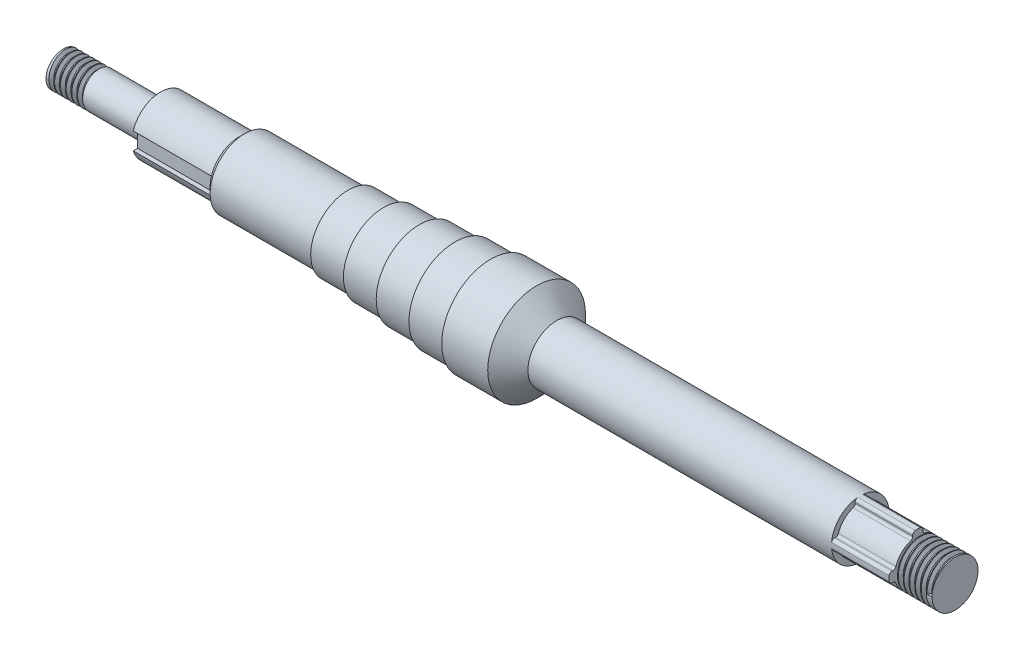
SolidWorks part; units mm, degrees
ref_plane "Front Plane" through (0, 0, 0) normal (0, 0, 1) x (1, 0, 0)
ref_plane "Top Plane" through (0, 0, 0) normal (0, 1, 0) x (1, 0, 0)
ref_plane "Right Plane" through (0, 0, 0) normal (1, 0, 0) x (0, 0, -1)
sketch "Sketch1" plane through (0, 0, 0) normal (0, 0, 1) x (1, 0, 0)
  line L0 (0, 0) -> (155.16, 0) construction
  line L4 (0, 0) -> (0, 3)
  line L5 (0, 3) -> (6.5, 3)
  line L11 (31.55, 6) -> (49.55, 6)
  line L12 (49.55, 6) -> (49.55, 6.5)
  line L13 (49.55, 6.5) -> (55.75, 6.5)
  line L17 (61.95, 7.5) -> (68.15, 7.5)
  line L18 (68.15, 7.5) -> (68.15, 8)
  line L31 (31.55, 6) -> (49.55, 6)
  line L36 (0, 0) -> (155.16, 0)
  line L38 (20.87, 5) -> (30.55, 5)
  line L40 (30.55, 5) -> (31.55, 6)
  line L41 (68.15, 8) -> (74.35, 8)
  line L42 (74.35, 8.5) -> (74.35, 8)
  line L43 (74.35, 8.5) -> (82.35, 8.5)
  line L44 (55.75, 6.5) -> (55.75, 7)
  line L45 (55.75, 7) -> (61.95, 7)
  line L46 (111.66, 5) -> (148.66, 5)
  line L47 (61.95, 7) -> (61.95, 7.5)
  line L48 (82.35, 8.5) -> (85.85, 5)
  line L49 (85.85, 5) -> (111.66, 5)
  line L50 (148.66, 5) -> (148.66, 4)
  line L51 (148.66, 4) -> (155.16, 4)
  line L52 (155.16, 4) -> (155.16, 0)
  line L54 (6.5, 3) -> (16.94, 3)
  line L55 (16.94, 3) -> (16.94, 5)
  line L56 (16.94, 5) -> (20.87, 5)
  dimension "D13" = 3
  dimension "D12" = 6.5
  dimension "D5" = 9.68
  dimension "D6" = 5
  dimension "D7" = 6
  dimension "D8" = 45
  dimension "D9" = 18
  dimension "D10" = 6.2
  dimension "D3" = 6.2
  dimension "D4" = 6.2
  dimension "D15" = 8
  dimension "D18" = 8.5
  dimension "D11" = 25.81
  dimension "D19" = 5
  dimension "D20" = 45
  dimension "D21" = 6.2
  dimension "D16" = 37
  dimension "D17" = 4
  dimension "D22" = 6.5
  dimension "D14" = 10.44
  dimension "D23" = 3.93
revolve "Revolve1" add sketch "Sketch1" angle 360 about L0
sketch3d "3DSketch1" plane through (0, 0, 0) normal (0, 0, 1) x (1, 0, 0)
thread "Thread1" pitch 1 method cut trim with end face yes profile "Thread Profile1" start angle 0, offset 0, length 0, pitch 1, diameter 8
ref_plane "Plane1" through (155.16, 0, 4) normal (0, -1, 0) x (0, 0, 1)
sketch "Thread Profile1" plane through (155.16, 0, 4) normal (0, -1, 0) x (0, 0, 1)
  line L0 (0, 0) -> (0, 1) construction
  line L11 (0, 0) -> (0, 0.875)
  line L12 (0, 0.875) -> (-0.5413, 0.5625)
  line L13 (-0.5413, 0.5625) -> (-0.5413, 0.3125)
  line L15 (-0.5413, 0.3125) -> (0, 0)
  line L17 (-0.5413, 0.4375) -> (0, 0.4375) construction
  point P2 (0, 0)
  dimension "Pitch" = 1
  dimension "Profile_Angle" = 60
  dimension "Profile_Land" = 0.25
  dimension "Profile_Height" = 0.5413
thread "Thread2" pitch 1 method cut profile "Thread Profile2" start angle 0, offset 0, length 0, pitch 1, diameter 6
ref_plane "Plane2" through (0, 0, -3) normal (0, -1, 0) x (0, 0, -1)
sketch "Thread Profile2" plane through (0, 0, -3) normal (0, -1, 0) x (0, 0, -1)
  line L0 (0, 0) -> (0, 1) construction
  line L11 (0, 0) -> (0, 0.875)
  line L12 (0, 0.875) -> (-0.5413, 0.5625)
  line L13 (-0.5413, 0.5625) -> (-0.5413, 0.3125)
  line L15 (-0.5413, 0.3125) -> (0, 0)
  line L17 (-0.5413, 0.4375) -> (0, 0.4375) construction
  point P2 (0, 0)
  dimension "Pitch" = 1
  dimension "Profile_Angle" = 60
  dimension "Profile_Land" = 0.25
  dimension "Profile_Height" = 0.5413
sketch "Sketch7" plane through (148.66, 0, 0) normal (1, 0, 0) x (0, 0, -1)
  line L0 (-0.881, 3.9018) -> (-0.881, 4.9218)
  line L1 (0.881, 3.9018) -> (0.881, 4.9218)
  line L2 (3.9018, 0.881) -> (4.9218, 0.881)
  line L3 (3.9018, -0.881) -> (4.9218, -0.881)
  line L4 (0.881, -3.9018) -> (0.881, -4.9218)
  line L5 (-0.881, -3.9018) -> (-0.881, -4.9218)
  line L6 (-3.9018, -0.881) -> (-4.9218, -0.881)
  line L7 (-3.9018, 0.881) -> (-4.9218, 0.881)
  circle A0 centre (0, 0) radius 4
  circle A1 centre (0, 0) radius 5 construction
  point P24 (0, 0)
  arc M3 (4, 0) -> (2.8284, -2.8284) centre (0, 0) cw
  circle M7 centre (0, 0) radius 5
  dimension "D1" = 8
  dimension "D2" = 1.02
  dimension "D3" = 4
extrude "Cut-Extrude2" cut sketch "Sketch7" against normal blind 10 contours A0 L2 L1 M7 | L4 L3 M7 M3 | A0 L6 L5 M7 | A0 L0 L7 M7 region at (148.66, 3.0174, 3.0174) region at (148.66, 3.0174, -3.0174) region at (148.66, -3.0174, 3.0174) region at (148.66, -3.0174, -3.0174)
fillet "Fillet1" radius 0.5 16 edges at (143.66, 0.881, -4.9218) (143.66, -0.881, 3.9018) (143.66, 3.9018, 0.881) (143.66, 0.881, 3.9018) (143.66, 0.881, 4.9218) (143.66, -0.881, 4.9218) (143.66, -3.9018, 0.881) (143.66, -4.9218, 0.881) (143.66, -3.9018, -0.881) (143.66, -4.9218, -0.881) (143.66, -0.881, -3.9018) (143.66, 0.881, -3.9018) (143.66, 3.9018, -0.881) (143.66, 4.9218, 0.881) (143.66, 4.9218, -0.881) (143.66, -0.881, -4.9218)
sketch "Sketch8" plane through (16.94, 0, 0) normal (-1, 0, 0) x (0, 0, 1)
  line L0 (-4.7697, 1.5) -> (-4, 1.5)
  line L1 (-4, 1.5) -> (-4, -1.5)
  line L2 (-4, -1.5) -> (-4.7697, -1.5)
  circle A0 centre (0, 0) radius 5 construction
  circle A1 centre (0, 0) radius 5 construction
  circle A4 centre (0, 0) radius 5
  point P14 (0, 0)
  point P15 (0, 0)
  dimension "D1" = 4
  dimension "D2" = 3
extrude "Cut-Extrude6" cut sketch "Sketch8" against normal blind 13.61 and the other way through all flip side to cut contours L0 L1 L2
pattern_circular "CirPattern1" count 2 over 360 about axis through (0, 0, 0) along (-1, 0, 0) of "Cut-Extrude6"
equation "\"Lab_Seal_Height\"= 0.089mm"
equation "\"Lab_Seal_Width\"= 12.7mm"
equation "\"LOx_Nut_Rad\"= 3mm"
equation "\"LOx_Nut_Len\"= 6.5mm"
equation "\"LOx_Taper_Len\"= 15.24mm"
equation "\"D13@Sketch1\"=\"LOx_Nut_Rad\""
equation "\"D12@Sketch1\"=\"LOx_Nut_Len\""
equation "\"LOx_Section_2\"= 9.68"
equation "\"LOx_End_Taper_Ang\"= 45deg"
equation "\"LOx_End_Rad\"= 5mm"
equation "\"D6@Sketch1\"=\"LOx_End_Rad\""
equation "\"D5@Sketch1\"=\"LOx_Section_2\""
equation "\"LOx_Bearing_Rad\"= 6mm"
equation "\"LOx_Bearing_Section_Width\"= 18mm"
equation "\"Lab_Seal_Len\"= 6.2mm"
equation "\"Lab_Seal_Stepup\"= .5"
equation "\"D7@Sketch1\"=\"LOx_Bearing_Rad\""
equation "\"D8@Sketch1\"=\"LOx_End_Taper_Ang\""
equation "\"D9@Sketch1\"=\"LOx_Bearing_Section_Width\""
equation "\"D10@Sketch1\"=\"Lab_Seal_Len\""
equation "\"D3@Sketch1\"=\"Lab_Seal_Len\""
equation "\"D4@Sketch1\"=\"Lab_Seal_Len\""
equation "\"Center_Section_Len\"= 8mm"
equation "\"Center_Section_Rad\"= 8.5mm"
equation "\"D15@Sketch1\"=\"Center_Section_Len\""
equation "\"D18@Sketch1\"=\"Center_Section_Rad\""
equation "\"Kero_Len\"= 25.81"
equation "\"Kero_Rad\"= 5mm"
equation "\"D11@Sketch1\"=\"Kero_Len\""
equation "\"D19@Sketch1\"=\"Kero_Rad\""
equation "\"D20@Sketch1\"=\"LOx_End_Taper_Ang\""
equation "\"D21@Sketch1\"=\"Lab_Seal_Len\""
equation "\"Shaft_Sleeve_Nut_Size\"= 4mm"
equation "\"Shaft_Sleeve_Nut_Width\"= 6.5mm"
equation "\"Distance to connection\"= 37mm"
equation "\"D16@Sketch1\"=\"Distance to connection\""
equation "\"D17@Sketch1\"=\"Shaft_Sleeve_Nut_Size\""
equation "\"D22@Sketch1\"=\"Shaft_Sleeve_Nut_Width\""
equation "\"LOx_Small_Section_Len\"= 10.44mm"
equation "\"D14@Sketch1\"=\"LOx_Small_Section_Len\""
equation "\"LOx_Keyway_Overhand\"= 3.93mm"
equation "\"D23@Sketch1\"=\"LOx_Keyway_Overhand\""
